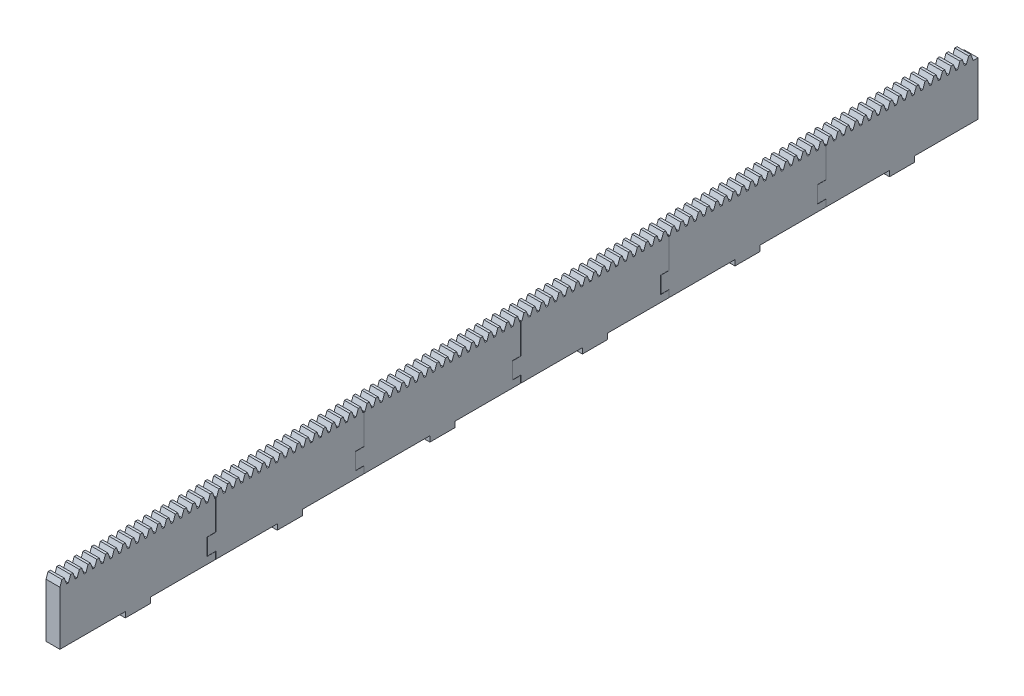
SolidWorks part; units mm, degrees
ref_plane "Спереди" through (0, 0, 0) normal (0, 0, 1) x (1, 0, 0)
ref_plane "Сверху" through (0, 0, 0) normal (0, 1, 0) x (1, 0, 0)
ref_plane "Справа" through (0, 0, 0) normal (1, 0, 0) x (0, 0, -1)
sketch "Эскиз2" plane through (0, 0, 0) normal (1, 0, 0) x (0, 0, -1)
  line L0 (-26.55, -90810.0672) -> (-26.55, -90381.6872) construction
  line L1 (-26.55, -90933.2872) -> (635.45, -90933.2872)
  line L2 (-26.55, -90933.2872) -> (-26.55, -90894.9119)
  line L3 (-26.55, -90894.9119) -> (635.45, -90894.9119)
  line L4 (635.45, -90933.2872) -> (635.45, -90894.9119)
  line L5 (635.45, -90810.0672) -> (635.45, -90381.6872) construction
  line L7 (-26.55, -90933.2872) -> (635.45, -90933.2872) construction
  dimension "D1" = 38.3753
  dimension "База_начала" = 26.55
  dimension "Длина_базы" = 662
  dimension "База_конца" = 635.45
  dimension "База_низа" = 90933.2872
extrude "Бобышка-Вытянуть1" add sketch "Эскиз2" along normal blind 10
sketch "Эскиз3" plane through (10, 0, 0) normal (1, 0, 0) x (0, 0, -1)
  line L0 (-26.55, -90894.9119) -> (-24.9125, -90890.4119)
  line L2 (-24.9125, -90890.4119) -> (-23.2265, -90890.4119)
  line L3 (-23.2265, -90890.4119) -> (-21.589, -90894.9119)
  line L4 (635.45, -90894.9119) -> (-26.55, -90894.9119) construction
  line L5 (-21.589, -90894.9119) -> (-26.55, -90894.9119)
  line L6 (-24.0695, -90890.4119) -> (-24.0695, -90894.9119) construction
  line L7 (-26.55, -90894.9119) -> (-26.55, -90933.2872) construction
  dimension "D1" = 1.686
  dimension "D2" = 4.961
  dimension "D3" = 4.5
extrude "Бобышка-Вытянуть2" add sketch "Эскиз3" against normal blind 10
pattern_linear "Линейный массив1" count 105 spacing 6.2832 along (0, 0, -1) of "Бобышка-Вытянуть2"
sketch "Лапки_рейки_эскиз" plane through (0, 0, 0) normal (1, 0, 0) x (0, 0, -1)
  line L0 (590.5046, -90933.2872) -> (570.5046, -90933.2872)
  line L1 (570.5046, -90933.2872) -> (570.5046, -90925.2872)
  line L2 (570.5046, -90925.2872) -> (590.5046, -90925.2872)
  line L3 (590.5046, -90925.2872) -> (590.5046, -90933.2872)
  line L4 (479.1606, -90933.2872) -> (459.1606, -90933.2872)
  line L5 (459.1606, -90933.2872) -> (459.1606, -90925.2872)
  line L6 (459.1606, -90925.2872) -> (479.1606, -90925.2872)
  line L7 (479.1606, -90925.2872) -> (479.1606, -90933.2872)
  line L8 (369.2048, -90933.2872) -> (349.2048, -90933.2872)
  line L9 (349.2048, -90933.2872) -> (349.2048, -90925.2872)
  line L10 (349.2048, -90925.2872) -> (369.2048, -90925.2872)
  line L11 (369.2048, -90925.2872) -> (369.2048, -90933.2872)
  line L12 (259.2491, -90933.2872) -> (239.2491, -90933.2872)
  line L13 (239.2491, -90933.2872) -> (239.2491, -90925.2872)
  line L14 (239.2491, -90925.2872) -> (259.2491, -90925.2872)
  line L15 (259.2491, -90925.2872) -> (259.2491, -90933.2872)
  line L16 (149.2933, -90933.2872) -> (129.2933, -90933.2872)
  line L17 (129.2933, -90933.2872) -> (129.2933, -90925.2872)
  line L18 (129.2933, -90925.2872) -> (149.2933, -90925.2872)
  line L19 (149.2933, -90925.2872) -> (149.2933, -90933.2872)
  line L20 (39.7431, -90933.2872) -> (19.7431, -90933.2872)
  line L21 (19.7431, -90933.2872) -> (19.7431, -90925.2872)
  line L22 (19.7431, -90925.2872) -> (39.7431, -90925.2872)
  line L23 (39.7431, -90925.2872) -> (39.7431, -90933.2872)
  dimension "X001" = 19.7431
  dimension "X002" = 20
  dimension "X003" = 89.5502
  dimension "X004" = 20
  dimension "X005" = 89.9557
  dimension "X006" = 20
  dimension "X007" = 89.9557
  dimension "X008" = 20
  dimension "X009" = 89.9557
  dimension "X010" = 20
  dimension "X011" = 91.3441
  dimension "X012" = 20
  dimension "Y001" = 90933.2872
  dimension "Y002" = 8
extrude "Лапки_рейки_к_полу" add sketch "Лапки_рейки_эскиз" against normal blind 22
sketch "Шипы_рейки_эскиз" plane through (0, 0, 0) normal (1, 0, 0) x (0, 0, -1)
  line L0 (589.5046, -90937.2872) -> (571.5046, -90937.2872)
  line L1 (571.5046, -90937.2872) -> (571.5046, -90933.2772)
  line L2 (571.5046, -90933.2772) -> (589.5046, -90933.2772)
  line L3 (589.5046, -90933.2772) -> (589.5046, -90937.2872)
  line L4 (478.1606, -90937.2872) -> (460.1606, -90937.2872)
  line L5 (460.1606, -90937.2872) -> (460.1606, -90933.2772)
  line L6 (460.1606, -90933.2772) -> (478.1606, -90933.2772)
  line L7 (478.1606, -90933.2772) -> (478.1606, -90937.2872)
  line L8 (368.2048, -90937.2872) -> (350.2048, -90937.2872)
  line L9 (350.2048, -90937.2872) -> (350.2048, -90933.2772)
  line L10 (350.2048, -90933.2772) -> (368.2048, -90933.2772)
  line L11 (368.2048, -90933.2772) -> (368.2048, -90937.2872)
  line L12 (258.2491, -90937.2872) -> (240.2491, -90937.2872)
  line L13 (240.2491, -90937.2872) -> (240.2491, -90933.2772)
  line L14 (240.2491, -90933.2772) -> (258.2491, -90933.2772)
  line L15 (258.2491, -90933.2772) -> (258.2491, -90937.2872)
  line L16 (148.2933, -90937.2872) -> (130.2933, -90937.2872)
  line L17 (130.2933, -90937.2872) -> (130.2933, -90933.2772)
  line L18 (130.2933, -90933.2772) -> (148.2933, -90933.2772)
  line L19 (148.2933, -90933.2772) -> (148.2933, -90937.2872)
  line L20 (38.7431, -90937.2872) -> (20.7431, -90937.2872)
  line L21 (20.7431, -90937.2872) -> (20.7431, -90933.2772)
  line L22 (20.7431, -90933.2772) -> (38.7431, -90933.2772)
  line L23 (38.7431, -90933.2772) -> (38.7431, -90937.2872)
  dimension "X001" = 20.7431
  dimension "X002" = 18
  dimension "X003" = 91.5502
  dimension "X004" = 18
  dimension "X005" = 91.9557
  dimension "X006" = 18
  dimension "X007" = 91.9557
  dimension "X008" = 18
  dimension "X009" = 91.9557
  dimension "X010" = 18
  dimension "X011" = 93.3441
  dimension "X012" = 18
  dimension "Y001" = 90937.2872
  dimension "Y002" = 4.01
extrude "Шипы_рейки_4мм" add sketch "Шипы_рейки_эскиз" along normal blind 10
sketch "Болты_рейки_эскиз" plane through (0, 0, 0) normal (0, 1, 0) x (1, 0, 0)
  circle A0 centre (-11, 580.5046) radius 2.75
  circle A1 centre (-11, 469.1606) radius 2.75
  circle A2 centre (-11, 359.2048) radius 2.75
  circle A3 centre (-11, 249.2491) radius 2.75
  circle A4 centre (-11, 139.2933) radius 2.75
  circle A5 centre (-11, 29.7431) radius 2.75
  dimension "Диаметр001" = 5.5
  dimension "Диаметр002" = 5.5
  dimension "Диаметр003" = 5.5
  dimension "Диаметр004" = 5.5
  dimension "Диаметр005" = 5.5
  dimension "Диаметр006" = 5.5
  dimension "X001" = 11
  dimension "Y001" = 29.7431
  dimension "Y002" = 109.5502
  dimension "Y003" = 109.9557
  dimension "Y004" = 109.9557
  dimension "Y005" = 109.9557
  dimension "Y006" = 111.3441
extrude "Болты_рейки_М5" cut sketch "Болты_рейки_эскиз" against normal through all and the other way through all
sketch "Гайки_рейки_эскиз" plane through (0, -90925.2872, 0) normal (0, 1, 0) x (1, 0, 0)
  line L0 (-6.208, 580.5046) -> (-8.604, 576.3546)
  line L1 (-8.604, 576.3546) -> (-13.396, 576.3546)
  line L2 (-13.396, 576.3546) -> (-15.792, 580.5046)
  line L3 (-15.792, 580.5046) -> (-13.396, 584.6546)
  line L4 (-13.396, 584.6546) -> (-8.604, 584.6546)
  line L5 (-8.604, 584.6546) -> (-6.208, 580.5046)
  line L6 (-6.208, 469.1606) -> (-8.604, 465.0106)
  line L7 (-8.604, 465.0106) -> (-13.396, 465.0106)
  line L8 (-13.396, 465.0106) -> (-15.792, 469.1606)
  line L9 (-15.792, 469.1606) -> (-13.396, 473.3106)
  line L10 (-13.396, 473.3106) -> (-8.604, 473.3106)
  line L11 (-8.604, 473.3106) -> (-6.208, 469.1606)
  line L12 (-6.208, 359.2048) -> (-8.604, 355.0548)
  line L13 (-8.604, 355.0548) -> (-13.396, 355.0548)
  line L14 (-13.396, 355.0548) -> (-15.792, 359.2048)
  line L15 (-15.792, 359.2048) -> (-13.396, 363.3548)
  line L16 (-13.396, 363.3548) -> (-8.604, 363.3548)
  line L17 (-8.604, 363.3548) -> (-6.208, 359.2048)
  line L18 (-6.208, 249.2491) -> (-8.604, 245.0991)
  line L19 (-8.604, 245.0991) -> (-13.396, 245.0991)
  line L20 (-13.396, 245.0991) -> (-15.792, 249.2491)
  line L21 (-15.792, 249.2491) -> (-13.396, 253.3991)
  line L22 (-13.396, 253.3991) -> (-8.604, 253.3991)
  line L23 (-8.604, 253.3991) -> (-6.208, 249.2491)
  line L24 (-6.208, 139.2933) -> (-8.604, 135.1433)
  line L25 (-8.604, 135.1433) -> (-13.396, 135.1433)
  line L26 (-13.396, 135.1433) -> (-15.792, 139.2933)
  line L27 (-15.792, 139.2933) -> (-13.396, 143.4433)
  line L28 (-13.396, 143.4433) -> (-8.604, 143.4433)
  line L29 (-8.604, 143.4433) -> (-6.208, 139.2933)
  line L30 (-6.208, 29.7431) -> (-8.604, 25.5931)
  line L31 (-8.604, 25.5931) -> (-13.396, 25.5931)
  line L32 (-13.396, 25.5931) -> (-15.792, 29.7431)
  line L33 (-15.792, 29.7431) -> (-13.396, 33.8931)
  line L34 (-13.396, 33.8931) -> (-8.604, 33.8931)
  line L35 (-8.604, 33.8931) -> (-6.208, 29.7431)
  dimension "X001" = 15.792
  dimension "X002" = 2.396
  dimension "X003" = 4.792
  dimension "X004" = 2.396
  dimension "Y001" = 25.5931
  dimension "Y002" = 4.15
  dimension "Y003" = 4.15
  dimension "Y004" = 101.2502
  dimension "Y005" = 4.15
  dimension "Y006" = 4.15
  dimension "Y007" = 101.6557
  dimension "Y008" = 4.15
  dimension "Y009" = 4.15
  dimension "Y010" = 101.6557
  dimension "Y011" = 4.15
  dimension "Y012" = 4.15
  dimension "Y013" = 101.6557
  dimension "Y014" = 4.15
  dimension "Y015" = 4.15
  dimension "Y016" = 103.0441
  dimension "Y017" = 4.15
  dimension "Y018" = 4.15
extrude "Гайки_рейки_М5_4_3мм" cut sketch "Гайки_рейки_эскиз" against normal blind 4.3
sketch "Секции_рейки_эскиз" plane through (0, 0, 0) normal (1, 0, 0) x (0, 0, -1)
  line L0 (525.7842, -90938.2872) -> (525.6342, -90938.2872)
  line L1 (525.6342, -90938.2872) -> (525.6342, -90928.3622)
  line L2 (525.6342, -90928.3622) -> (519.6342, -90928.3622)
  line L3 (519.6342, -90928.3622) -> (519.6342, -90916.2122)
  line L4 (519.6342, -90916.2122) -> (525.6342, -90916.2122)
  line L5 (525.6342, -90916.2122) -> (525.6342, -90888.2872)
  line L6 (525.6342, -90888.2872) -> (525.7842, -90888.2872)
  line L7 (525.7842, -90888.2872) -> (525.7842, -90916.3622)
  line L8 (525.7842, -90916.3622) -> (519.7842, -90916.3622)
  line L9 (519.7842, -90916.3622) -> (519.7842, -90928.2122)
  line L10 (519.7842, -90928.2122) -> (525.7842, -90928.2122)
  line L11 (525.7842, -90928.2122) -> (525.7842, -90938.2872)
  line L12 (412.6869, -90938.2872) -> (412.5369, -90938.2872)
  line L13 (412.5369, -90938.2872) -> (412.5369, -90928.3622)
  line L14 (412.5369, -90928.3622) -> (406.5369, -90928.3622)
  line L15 (406.5369, -90928.3622) -> (406.5369, -90916.2122)
  line L16 (406.5369, -90916.2122) -> (412.5369, -90916.2122)
  line L17 (412.5369, -90916.2122) -> (412.5369, -90888.2872)
  line L18 (412.5369, -90888.2872) -> (412.6869, -90888.2872)
  line L19 (412.6869, -90888.2872) -> (412.6869, -90916.3622)
  line L20 (412.6869, -90916.3622) -> (406.6869, -90916.3622)
  line L21 (406.6869, -90916.3622) -> (406.6869, -90928.2122)
  line L22 (406.6869, -90928.2122) -> (412.6869, -90928.2122)
  line L23 (412.6869, -90928.2122) -> (412.6869, -90938.2872)
  line L24 (305.8727, -90938.2872) -> (305.7227, -90938.2872)
  line L25 (305.7227, -90938.2872) -> (305.7227, -90928.3622)
  line L26 (305.7227, -90928.3622) -> (299.7227, -90928.3622)
  line L27 (299.7227, -90928.3622) -> (299.7227, -90916.2122)
  line L28 (299.7227, -90916.2122) -> (305.7227, -90916.2122)
  line L29 (305.7227, -90916.2122) -> (305.7227, -90888.2872)
  line L30 (305.7227, -90888.2872) -> (305.8727, -90888.2872)
  line L31 (305.8727, -90888.2872) -> (305.8727, -90916.3622)
  line L32 (305.8727, -90916.3622) -> (299.8727, -90916.3622)
  line L33 (299.8727, -90916.3622) -> (299.8727, -90928.2122)
  line L34 (299.8727, -90928.2122) -> (305.8727, -90928.2122)
  line L35 (305.8727, -90928.2122) -> (305.8727, -90938.2872)
  line L36 (192.7754, -90938.2872) -> (192.6254, -90938.2872)
  line L37 (192.6254, -90938.2872) -> (192.6254, -90928.3622)
  line L38 (192.6254, -90928.3622) -> (186.6254, -90928.3622)
  line L39 (186.6254, -90928.3622) -> (186.6254, -90916.2122)
  line L40 (186.6254, -90916.2122) -> (192.6254, -90916.2122)
  line L41 (192.6254, -90916.2122) -> (192.6254, -90888.2872)
  line L42 (192.6254, -90888.2872) -> (192.7754, -90888.2872)
  line L43 (192.7754, -90888.2872) -> (192.7754, -90916.3622)
  line L44 (192.7754, -90916.3622) -> (186.7754, -90916.3622)
  line L45 (186.7754, -90916.3622) -> (186.7754, -90928.2122)
  line L46 (186.7754, -90928.2122) -> (192.7754, -90928.2122)
  line L47 (192.7754, -90928.2122) -> (192.7754, -90938.2872)
  line L48 (85.9612, -90938.2872) -> (85.8112, -90938.2872)
  line L49 (85.8112, -90938.2872) -> (85.8112, -90928.3622)
  line L50 (85.8112, -90928.3622) -> (79.8112, -90928.3622)
  line L51 (79.8112, -90928.3622) -> (79.8112, -90916.2122)
  line L52 (79.8112, -90916.2122) -> (85.8112, -90916.2122)
  line L53 (85.8112, -90916.2122) -> (85.8112, -90888.2872)
  line L54 (85.8112, -90888.2872) -> (85.9612, -90888.2872)
  line L55 (85.9612, -90888.2872) -> (85.9612, -90916.3622)
  line L56 (85.9612, -90916.3622) -> (79.9612, -90916.3622)
  line L57 (79.9612, -90916.3622) -> (79.9612, -90928.2122)
  line L58 (79.9612, -90928.2122) -> (85.9612, -90928.2122)
  line L59 (85.9612, -90928.2122) -> (85.9612, -90938.2872)
  dimension "X001" = 79.8112
  dimension "X002" = 0.15
  dimension "X003" = 5.85
  dimension "X004" = 0.15
  dimension "X005" = 100.6642
  dimension "X006" = 0.15
  dimension "X007" = 5.85
  dimension "X008" = 0.15
  dimension "X009" = 106.9473
  dimension "X010" = 0.15
  dimension "X011" = 5.85
  dimension "X012" = 0.15
  dimension "X013" = 100.6642
  dimension "X014" = 0.15
  dimension "X015" = 5.85
  dimension "X016" = 0.15
  dimension "X017" = 106.9473
  dimension "X018" = 0.15
  dimension "X019" = 5.85
  dimension "X020" = 0.15
  dimension "Y001" = 90938.2872
  dimension "Y002" = 9.925
  dimension "Y003" = 0.15
  dimension "Y004" = 11.85
  dimension "Y005" = 0.15
  dimension "Y006" = 27.925
extrude "Секции_рейки_шип_паз_6шт" cut sketch "Секции_рейки_эскиз" against normal through all and the other way through all
sketch "Торцы_рейки_эскиз" plane through (0, 0, 0) normal (1, 0, 0) x (0, 0, -1)
  line L0 (647.2604, -90939.2872) -> (635.3, -90939.2872)
  line L1 (635.3, -90939.2872) -> (635.3, -90883.2872)
  line L2 (635.3, -90883.2872) -> (647.2604, -90883.2872)
  line L3 (647.2604, -90883.2872) -> (647.2604, -90939.2872)
  line L4 (-26.4, -90939.2872) -> (-36.55, -90939.2872)
  line L5 (-36.55, -90939.2872) -> (-36.55, -90883.2872)
  line L6 (-36.55, -90883.2872) -> (-26.4, -90883.2872)
  line L7 (-26.4, -90883.2872) -> (-26.4, -90939.2872)
  dimension "X001" = 36.55
  dimension "X002" = 10.15
  dimension "X003" = 661.7
  dimension "X004" = 11.9604
  dimension "Y001" = 90939.2872
  dimension "Y002" = 56
extrude "Торцы_рейки_зазор_0_15мм" cut sketch "Торцы_рейки_эскиз" against normal through all and the other way through all
equation "\"Ширина груза\"= 160"
equation "\"Глубина груза\"= 240"
equation "\"Высота груза\"= 160"
equation "\"Ширина ячейки\"= \"Ширина груза\" + 10"
equation "\"Глубина ячейки\"= \"Глубина груза\" + 10"
equation "\"Высота ячейки\"= \"Высота груза\" + 10 + 13"
equation "\"Колво ячеек ширина\"= 2"
equation "\"Колво ячеек высота\"= 2"
equation "\"Толщина стенки\" = \"Толщина тонких панелей\""
equation "\"Крепление дверцы\"= 5 "
equation "\"Ширина рейки\"= \"Толщина шестерни\""
equation "\"Высота рейки\"= 20"
equation "\"Высота пола\" = 2*\"Толщина тонких панелей\""
equation "\"Колво полозьев\"= 5"
equation "\"Отступ рейки\"= 20"
equation "\"Глубина каретки\"= \"Глубина ячейки\" + 30 + \"Мотор Y высота корпуса\" + 20"
equation "\"Длинна рейки\" = (\"Ширина ячейки\"+\"Толщина вертикальных стенок\"+\"Крепление дверцы\")*\"Колво ячеек ширина\"+\"Ширина ячейки выгрузки\"*\"Колво выгрузки\"+\"Толщина вертикальных стенок\"+2*\"Отступ крепления мотора фиксации\"-\"Крепление дверцы\"*\"Колво ячеек ширина\""
equation "\"Отступ шпильки\"= 26"
equation "\"Диаметр шпильки\"= 5"
equation "\"Длинна шпильки\" = (\"Высота ячейки\"+\"Толщина горизонтальных плит\"+\"Высота пола\")*\"Колво ячеек высота\"+2*(\"Толщина горизонтальных плит\"+\"Отступ рейки\")"
equation "\"Ширина пластины\"= 50  "
equation "\"Высота зона выгрузки\"= \"Высота ячейки\" * 2 + \"Толщина стенки\" * 2"
equation "\"Колво выгрузки\"= 1"
equation "\"Ширина ячейки выгрузки\" = \"Ширина ячейки\"+\"Толщина вертикальных стенок\"+2*\"Отступ крепления мотора фиксации\""
equation "\"Отступ крепления мотора фиксации\" = (\"Ширина пластины\"+20-\"Толщина вертикальных стенок\")/2"
equation "\"Мотор X ширина корпуса\"= 42.3"
equation "\"Мотор X высота корпуса\"= 42.3"
equation "\"Мотор X длина корпуса\"= 40"
equation "\"Мотор X вылет вала\"= 19.8"
equation "\"Мотор Y ширина корпуса\"= 42.3"
equation "\"Мотор Y высота корпуса\"= 42.3"
equation "\"Мотор Y длина корпуса\"= 48"
equation "\"Мотор Y вылет вала\"= 30"
equation "\"Мотор Z ширина корпуса\"= 42"
equation "\"Мотор Z высота корпуса\"= 42"
equation "\"Мотор Z длина корпуса\"= 40"
equation "\"Мотор Z вылет вала\"= 23"
equation "\"Мотор диаметр вала ПРЕДВ\"= 5"
equation "\"Мотор шаг крепления ПРЕДВ\"= 31"
equation "\"Мотор диаметр отверстий ПРЕДВ\"= 3"
equation "\"Мотор глубина отверстий ПРЕДВ\"= 4.5"
equation "\"Мотор диаметр буртика ПРЕДВ\"= 22"
equation "\"Мотор высота буртика ПРЕДВ\"= 2"
equation "\"Мотор диаметр шкива ПРЕДВ\"= 16"
equation "\"Мотор длина шкива ПРЕДВ\"= 12"
equation "\"Мотор отступ шкива ПРЕДВ\"= 5"
equation "\"Мотор X шаг градусов\"= 1.8"
equation "\"Мотор Y шаг градусов\"= 1.8"
equation "\"Мотор Z шаг градусов\"= 1.8"
equation "\"Мотор Y диаметр ротора\"= 25.78"
equation "\"Толщина шестерни\"= 10"
equation "\"D1@Эскиз2\" = \"Высота рейки от пола\""
equation "\"D1@Бобышка-Вытянуть1\"=\"Толщина шестерни\""
equation "\"D1@Бобышка-Вытянуть2\"=\"Толщина шестерни\""
equation "\"Высота рейки от пола\"= 38.3752522580543"
equation "\"X001@Лапки_рейки_эскиз\" = \"Привязка_X001_Лапки_рейки_эскиз\""
equation "\"X003@Лапки_рейки_эскиз\" = -1*((\"Крепление рейки 2\"-\"Смещение рейки по Z\"+(10))-(\"Крепление рейки 1\"-\"Смещение рейки по Z\"+(-10)))"
equation "\"X005@Лапки_рейки_эскиз\" = -1*((\"Крепление рейки 3\"-\"Смещение рейки по Z\"+(10))-(\"Крепление рейки 2\"-\"Смещение рейки по Z\"+(-10)))"
equation "\"X007@Лапки_рейки_эскиз\" = -1*((\"Крепление рейки 4\"-\"Смещение рейки по Z\"+(10))-(\"Крепление рейки 3\"-\"Смещение рейки по Z\"+(-10)))"
equation "\"X009@Лапки_рейки_эскиз\" = -1*((\"Крепление рейки 5\"-\"Смещение рейки по Z\"+(10))-(\"Крепление рейки 4\"-\"Смещение рейки по Z\"+(-10)))"
equation "\"X011@Лапки_рейки_эскиз\" = -1*((\"Крепление рейки 6\"-\"Смещение рейки по Z\"+(10))-(\"Крепление рейки 5\"-\"Смещение рейки по Z\"+(-10)))"
equation "\"X001@Шипы_рейки_эскиз\" = \"Привязка_X001_Шипы_рейки_эскиз\""
equation "\"X003@Шипы_рейки_эскиз\" = -1*((\"Крепление рейки 2\"-\"Смещение рейки по Z\"+(9))-(\"Крепление рейки 1\"-\"Смещение рейки по Z\"+(-9)))"
equation "\"X005@Шипы_рейки_эскиз\" = -1*((\"Крепление рейки 3\"-\"Смещение рейки по Z\"+(9))-(\"Крепление рейки 2\"-\"Смещение рейки по Z\"+(-9)))"
equation "\"X007@Шипы_рейки_эскиз\" = -1*((\"Крепление рейки 4\"-\"Смещение рейки по Z\"+(9))-(\"Крепление рейки 3\"-\"Смещение рейки по Z\"+(-9)))"
equation "\"X009@Шипы_рейки_эскиз\" = -1*((\"Крепление рейки 5\"-\"Смещение рейки по Z\"+(9))-(\"Крепление рейки 4\"-\"Смещение рейки по Z\"+(-9)))"
equation "\"X011@Шипы_рейки_эскиз\" = -1*((\"Крепление рейки 6\"-\"Смещение рейки по Z\"+(9))-(\"Крепление рейки 5\"-\"Смещение рейки по Z\"+(-9)))"
equation "\"Y001@Болты_рейки_эскиз\" = \"Привязка_Y001_Болты_рейки_эскиз\""
equation "\"Y002@Болты_рейки_эскиз\" = -1*((\"Крепление рейки 2\"-\"Смещение рейки по Z\"+(0))-(\"Крепление рейки 1\"-\"Смещение рейки по Z\"+(0)))"
equation "\"Y003@Болты_рейки_эскиз\" = -1*((\"Крепление рейки 3\"-\"Смещение рейки по Z\"+(0))-(\"Крепление рейки 2\"-\"Смещение рейки по Z\"+(0)))"
equation "\"Y004@Болты_рейки_эскиз\" = -1*((\"Крепление рейки 4\"-\"Смещение рейки по Z\"+(0))-(\"Крепление рейки 3\"-\"Смещение рейки по Z\"+(0)))"
equation "\"Y005@Болты_рейки_эскиз\" = -1*((\"Крепление рейки 5\"-\"Смещение рейки по Z\"+(0))-(\"Крепление рейки 4\"-\"Смещение рейки по Z\"+(0)))"
equation "\"Y006@Болты_рейки_эскиз\" = -1*((\"Крепление рейки 6\"-\"Смещение рейки по Z\"+(0))-(\"Крепление рейки 5\"-\"Смещение рейки по Z\"+(0)))"
equation "\"Y001@Гайки_рейки_эскиз\" = \"Привязка_Y001_Гайки_рейки_эскиз\""
equation "\"Y004@Гайки_рейки_эскиз\" = -1*((\"Крепление рейки 2\"-\"Смещение рейки по Z\"+(4.15))-(\"Крепление рейки 1\"-\"Смещение рейки по Z\"+(-4.15)))"
equation "\"Y007@Гайки_рейки_эскиз\" = -1*((\"Крепление рейки 3\"-\"Смещение рейки по Z\"+(4.15))-(\"Крепление рейки 2\"-\"Смещение рейки по Z\"+(-4.15)))"
equation "\"Y010@Гайки_рейки_эскиз\" = -1*((\"Крепление рейки 4\"-\"Смещение рейки по Z\"+(4.15))-(\"Крепление рейки 3\"-\"Смещение рейки по Z\"+(-4.15)))"
equation "\"Y013@Гайки_рейки_эскиз\" = -1*((\"Крепление рейки 5\"-\"Смещение рейки по Z\"+(4.15))-(\"Крепление рейки 4\"-\"Смещение рейки по Z\"+(-4.15)))"
equation "\"Y016@Гайки_рейки_эскиз\" = -1*((\"Крепление рейки 6\"-\"Смещение рейки по Z\"+(4.15))-(\"Крепление рейки 5\"-\"Смещение рейки по Z\"+(-4.15)))"
equation "\"X003@Торцы_рейки_эскиз\" = \"Длина рейки для печати\""
equation "\"Толщина тонких панелей\" = 6"
equation "\"Толщина вертикальных стенок\" = 6"
equation "\"Толщина горизонтальных плит\" = 6"
equation "\"Базовая высота корпуса\"= (\"Высота ячейки\"+\"Толщина тонких панелей\"+\"Высота пола\")*\"Колво ячеек высота\"+6*\"Толщина тонких панелей\"+\"Мотор X ширина корпуса\"+\"Мотор Y ширина корпуса\"+75"
equation "\"Высота корпуса\"= (\"Высота ячейки\"+\"Толщина горизонтальных плит\"+\"Высота пола\")*\"Колво ячеек высота\"+2*\"Толщина горизонтальных плит\"+4*\"Толщина тонких панелей\"+\"Мотор X ширина корпуса\"+\"Мотор Y ширина корпуса\"+75"
equation "\"Смещение центра корпуса\"= (\"Высота корпуса\"-\"Базовая высота корпуса\")/2-(\"Толщина горизонтальных плит\"-\"Толщина тонких панелей\")"
equation "\"Отметка пола\"= -\"Базовая высота корпуса\"/2+\"Толщина тонких панелей\""
equation "\"Отметка потолка\"= \"Отметка пола\"+\"Высота корпуса\"-2*\"Толщина горизонтальных плит\""
equation "\"Отметка верхней полки\"= \"Отметка потолка\"-(28+\"Толщина тонких панелей\")-\"Высота ячейки\"-\"Высота пола\""
equation "\"Отметка нижней полки\"= \"Отметка верхней полки\"-\"Высота ячейки\"-\"Высота пола\"-\"Толщина горизонтальных плит\""
equation "\"X001@Торцы_рейки_эскиз\" = \"Длинна рейки\"-\"База_конца@Эскиз2\"+10"
equation "\"dT\"= (\"Толщина вертикальных стенок\"-\"Толщина тонких панелей\")"
equation "\"dW\"= \"Ширина ячейки\"-430+2*\"dT\"/3"
equation "\"Торцевой зазор рейки\"= 0.15"
equation "\"Зазор стыка рейки\"= 0.15"
equation "\"Длина шипа стыка рейки\"= 6"
equation "\"Шаг зубьев рейки\"= 2*pi"
equation "\"Начало рейки для печати\"= \"Длинна рейки\"-\"База_конца@Эскиз2\"-\"Торцевой зазор рейки\""
equation "\"Длина рейки для печати\"= \"Длинна рейки\"-2*\"Торцевой зазор рейки\""
equation "\"Ноль впадин рейки\"= \"Длинна рейки\"-\"База_конца@Эскиз2\"-(\"D2@Эскиз3\"+\"Шаг зубьев рейки\")/2"
equation "\"Стык рейки 1\"= \"Ноль впадин рейки\"-\"Шаг зубьев рейки\"*int((\"Ноль впадин рейки\"-(\"Начало рейки для печати\"-1*\"Длина рейки для печати\"/6))/\"Шаг зубьев рейки\"+0.5)"
equation "\"Стык рейки 2\"= \"Ноль впадин рейки\"-\"Шаг зубьев рейки\"*int((\"Ноль впадин рейки\"-(\"Начало рейки для печати\"-2*\"Длина рейки для печати\"/6))/\"Шаг зубьев рейки\"+0.5)"
equation "\"Стык рейки 3\"= \"Ноль впадин рейки\"-\"Шаг зубьев рейки\"*int((\"Ноль впадин рейки\"-(\"Начало рейки для печати\"-3*\"Длина рейки для печати\"/6))/\"Шаг зубьев рейки\"+0.5)"
equation "\"Стык рейки 4\"= \"Ноль впадин рейки\"-\"Шаг зубьев рейки\"*int((\"Ноль впадин рейки\"-(\"Начало рейки для печати\"-4*\"Длина рейки для печати\"/6))/\"Шаг зубьев рейки\"+0.5)"
equation "\"Стык рейки 5\"= \"Ноль впадин рейки\"-\"Шаг зубьев рейки\"*int((\"Ноль впадин рейки\"-(\"Начало рейки для печати\"-5*\"Длина рейки для печати\"/6))/\"Шаг зубьев рейки\"+0.5)"
equation "\"X001@Секции_рейки_эскиз\" = 1*((\"Стык рейки 1\"+\"Длина шипа стыка рейки\"+\"Зазор стыка рейки\"/2)-0)"
equation "\"X002@Секции_рейки_эскиз\" = -1*((\"Стык рейки 1\"+\"Длина шипа стыка рейки\"-\"Зазор стыка рейки\"/2)-(\"Стык рейки 1\"+\"Длина шипа стыка рейки\"+\"Зазор стыка рейки\"/2))"
equation "\"X003@Секции_рейки_эскиз\" = -1*((\"Стык рейки 1\"+\"Зазор стыка рейки\"/2)-(\"Стык рейки 1\"+\"Длина шипа стыка рейки\"-\"Зазор стыка рейки\"/2))"
equation "\"X004@Секции_рейки_эскиз\" = -1*((\"Стык рейки 1\"-\"Зазор стыка рейки\"/2)-(\"Стык рейки 1\"+\"Зазор стыка рейки\"/2))"
equation "\"X005@Секции_рейки_эскиз\" = -1*((\"Стык рейки 2\"+\"Длина шипа стыка рейки\"+\"Зазор стыка рейки\"/2)-(\"Стык рейки 1\"-\"Зазор стыка рейки\"/2))"
equation "\"X006@Секции_рейки_эскиз\" = -1*((\"Стык рейки 2\"+\"Длина шипа стыка рейки\"-\"Зазор стыка рейки\"/2)-(\"Стык рейки 2\"+\"Длина шипа стыка рейки\"+\"Зазор стыка рейки\"/2))"
equation "\"X007@Секции_рейки_эскиз\" = -1*((\"Стык рейки 2\"+\"Зазор стыка рейки\"/2)-(\"Стык рейки 2\"+\"Длина шипа стыка рейки\"-\"Зазор стыка рейки\"/2))"
equation "\"X008@Секции_рейки_эскиз\" = -1*((\"Стык рейки 2\"-\"Зазор стыка рейки\"/2)-(\"Стык рейки 2\"+\"Зазор стыка рейки\"/2))"
equation "\"X009@Секции_рейки_эскиз\" = -1*((\"Стык рейки 3\"+\"Длина шипа стыка рейки\"+\"Зазор стыка рейки\"/2)-(\"Стык рейки 2\"-\"Зазор стыка рейки\"/2))"
equation "\"X010@Секции_рейки_эскиз\" = -1*((\"Стык рейки 3\"+\"Длина шипа стыка рейки\"-\"Зазор стыка рейки\"/2)-(\"Стык рейки 3\"+\"Длина шипа стыка рейки\"+\"Зазор стыка рейки\"/2))"
equation "\"X011@Секции_рейки_эскиз\" = -1*((\"Стык рейки 3\"+\"Зазор стыка рейки\"/2)-(\"Стык рейки 3\"+\"Длина шипа стыка рейки\"-\"Зазор стыка рейки\"/2))"
equation "\"X012@Секции_рейки_эскиз\" = -1*((\"Стык рейки 3\"-\"Зазор стыка рейки\"/2)-(\"Стык рейки 3\"+\"Зазор стыка рейки\"/2))"
equation "\"X013@Секции_рейки_эскиз\" = -1*((\"Стык рейки 4\"+\"Длина шипа стыка рейки\"+\"Зазор стыка рейки\"/2)-(\"Стык рейки 3\"-\"Зазор стыка рейки\"/2))"
equation "\"X014@Секции_рейки_эскиз\" = -1*((\"Стык рейки 4\"+\"Длина шипа стыка рейки\"-\"Зазор стыка рейки\"/2)-(\"Стык рейки 4\"+\"Длина шипа стыка рейки\"+\"Зазор стыка рейки\"/2))"
equation "\"X015@Секции_рейки_эскиз\" = -1*((\"Стык рейки 4\"+\"Зазор стыка рейки\"/2)-(\"Стык рейки 4\"+\"Длина шипа стыка рейки\"-\"Зазор стыка рейки\"/2))"
equation "\"X016@Секции_рейки_эскиз\" = -1*((\"Стык рейки 4\"-\"Зазор стыка рейки\"/2)-(\"Стык рейки 4\"+\"Зазор стыка рейки\"/2))"
equation "\"X017@Секции_рейки_эскиз\" = -1*((\"Стык рейки 5\"+\"Длина шипа стыка рейки\"+\"Зазор стыка рейки\"/2)-(\"Стык рейки 4\"-\"Зазор стыка рейки\"/2))"
equation "\"X018@Секции_рейки_эскиз\" = -1*((\"Стык рейки 5\"+\"Длина шипа стыка рейки\"-\"Зазор стыка рейки\"/2)-(\"Стык рейки 5\"+\"Длина шипа стыка рейки\"+\"Зазор стыка рейки\"/2))"
equation "\"X019@Секции_рейки_эскиз\" = -1*((\"Стык рейки 5\"+\"Зазор стыка рейки\"/2)-(\"Стык рейки 5\"+\"Длина шипа стыка рейки\"-\"Зазор стыка рейки\"/2))"
equation "\"X020@Секции_рейки_эскиз\" = -1*((\"Стык рейки 5\"-\"Зазор стыка рейки\"/2)-(\"Стык рейки 5\"+\"Зазор стыка рейки\"/2))"
equation "\"Правый конец рейки\"= -\"Ширина ячейки\"-65"
equation "\"Левый конец рейки\"= \"Правый конец рейки\"+\"Длинна рейки\""
equation "\"Впадина рейки в сборке\"= \"Левый конец рейки\"-(\"Шаг зубьев рейки\"+4.961)/2"
equation "\"Стык рейки в сборке 1\"= \"Впадина рейки в сборке\"-\"Шаг зубьев рейки\"*int((\"Впадина рейки в сборке\"-(\"Левый конец рейки\"-0.15-1*(\"Длинна рейки\"-0.3)/6))/\"Шаг зубьев рейки\"+0.5)"
equation "\"Стык рейки в сборке 2\"= \"Впадина рейки в сборке\"-\"Шаг зубьев рейки\"*int((\"Впадина рейки в сборке\"-(\"Левый конец рейки\"-0.15-2*(\"Длинна рейки\"-0.3)/6))/\"Шаг зубьев рейки\"+0.5)"
equation "\"Стык рейки в сборке 3\"= \"Впадина рейки в сборке\"-\"Шаг зубьев рейки\"*int((\"Впадина рейки в сборке\"-(\"Левый конец рейки\"-0.15-3*(\"Длинна рейки\"-0.3)/6))/\"Шаг зубьев рейки\"+0.5)"
equation "\"Стык рейки в сборке 4\"= \"Впадина рейки в сборке\"-\"Шаг зубьев рейки\"*int((\"Впадина рейки в сборке\"-(\"Левый конец рейки\"-0.15-4*(\"Длинна рейки\"-0.3)/6))/\"Шаг зубьев рейки\"+0.5)"
equation "\"Стык рейки в сборке 5\"= \"Впадина рейки в сборке\"-\"Шаг зубьев рейки\"*int((\"Впадина рейки в сборке\"-(\"Левый конец рейки\"-0.15-5*(\"Длинна рейки\"-0.3)/6))/\"Шаг зубьев рейки\"+0.5)"
equation "\"Крепление рейки 1\"= (\"Левый конец рейки\"-0.15+\"Стык рейки в сборке 1\")/2"
equation "\"Крепление рейки 2\"= (\"Стык рейки в сборке 1\"+\"Стык рейки в сборке 2\")/2"
equation "\"Крепление рейки 3\"= (\"Стык рейки в сборке 2\"+\"Стык рейки в сборке 3\")/2"
equation "\"Крепление рейки 4\"= (\"Стык рейки в сборке 3\"+\"Стык рейки в сборке 4\")/2"
equation "\"Крепление рейки 5\"= (\"Стык рейки в сборке 4\"+\"Стык рейки в сборке 5\")/2"
equation "\"Крепление рейки 6\"= (\"Стык рейки в сборке 5\"+\"Правый конец рейки\"+0.15)/2"
equation "\"Смещение рейки по Z\"= \"База_конца@Эскиз2\"+\"Правый конец рейки\""
equation "\"Привязка_X001_Лапки_рейки_эскиз\"= 1*((\"Крепление рейки 1\"-\"Смещение рейки по Z\"+(10))-0)"
equation "\"X002@Лапки_рейки_эскиз\" = -1*((\"Крепление рейки 1\"-\"Смещение рейки по Z\"+(-10))-(\"Крепление рейки 1\"-\"Смещение рейки по Z\"+(10)))"
equation "\"X004@Лапки_рейки_эскиз\" = -1*((\"Крепление рейки 2\"-\"Смещение рейки по Z\"+(-10))-(\"Крепление рейки 2\"-\"Смещение рейки по Z\"+(10)))"
equation "\"X006@Лапки_рейки_эскиз\" = -1*((\"Крепление рейки 3\"-\"Смещение рейки по Z\"+(-10))-(\"Крепление рейки 3\"-\"Смещение рейки по Z\"+(10)))"
equation "\"X008@Лапки_рейки_эскиз\" = -1*((\"Крепление рейки 4\"-\"Смещение рейки по Z\"+(-10))-(\"Крепление рейки 4\"-\"Смещение рейки по Z\"+(10)))"
equation "\"X010@Лапки_рейки_эскиз\" = -1*((\"Крепление рейки 5\"-\"Смещение рейки по Z\"+(-10))-(\"Крепление рейки 5\"-\"Смещение рейки по Z\"+(10)))"
equation "\"X012@Лапки_рейки_эскиз\" = -1*((\"Крепление рейки 6\"-\"Смещение рейки по Z\"+(-10))-(\"Крепление рейки 6\"-\"Смещение рейки по Z\"+(10)))"
equation "\"Привязка_X001_Шипы_рейки_эскиз\"= 1*((\"Крепление рейки 1\"-\"Смещение рейки по Z\"+(9))-0)"
equation "\"X002@Шипы_рейки_эскиз\" = -1*((\"Крепление рейки 1\"-\"Смещение рейки по Z\"+(-9))-(\"Крепление рейки 1\"-\"Смещение рейки по Z\"+(9)))"
equation "\"X004@Шипы_рейки_эскиз\" = -1*((\"Крепление рейки 2\"-\"Смещение рейки по Z\"+(-9))-(\"Крепление рейки 2\"-\"Смещение рейки по Z\"+(9)))"
equation "\"X006@Шипы_рейки_эскиз\" = -1*((\"Крепление рейки 3\"-\"Смещение рейки по Z\"+(-9))-(\"Крепление рейки 3\"-\"Смещение рейки по Z\"+(9)))"
equation "\"X008@Шипы_рейки_эскиз\" = -1*((\"Крепление рейки 4\"-\"Смещение рейки по Z\"+(-9))-(\"Крепление рейки 4\"-\"Смещение рейки по Z\"+(9)))"
equation "\"X010@Шипы_рейки_эскиз\" = -1*((\"Крепление рейки 5\"-\"Смещение рейки по Z\"+(-9))-(\"Крепление рейки 5\"-\"Смещение рейки по Z\"+(9)))"
equation "\"X012@Шипы_рейки_эскиз\" = -1*((\"Крепление рейки 6\"-\"Смещение рейки по Z\"+(-9))-(\"Крепление рейки 6\"-\"Смещение рейки по Z\"+(9)))"
equation "\"Привязка_Y001_Болты_рейки_эскиз\"= 1*((\"Крепление рейки 1\"-\"Смещение рейки по Z\"+(0))-0)"
equation "\"Привязка_Y001_Гайки_рейки_эскиз\"= 1*((\"Крепление рейки 1\"-\"Смещение рейки по Z\"+(4.15))-0)"
equation "\"Y002@Гайки_рейки_эскиз\" = -1*((\"Крепление рейки 1\"-\"Смещение рейки по Z\"+(0))-(\"Крепление рейки 1\"-\"Смещение рейки по Z\"+(4.15)))"
equation "\"Y003@Гайки_рейки_эскиз\" = -1*((\"Крепление рейки 1\"-\"Смещение рейки по Z\"+(-4.15))-(\"Крепление рейки 1\"-\"Смещение рейки по Z\"+(0)))"
equation "\"Y005@Гайки_рейки_эскиз\" = -1*((\"Крепление рейки 2\"-\"Смещение рейки по Z\"+(0))-(\"Крепление рейки 2\"-\"Смещение рейки по Z\"+(4.15)))"
equation "\"Y006@Гайки_рейки_эскиз\" = -1*((\"Крепление рейки 2\"-\"Смещение рейки по Z\"+(-4.15))-(\"Крепление рейки 2\"-\"Смещение рейки по Z\"+(0)))"
equation "\"Y008@Гайки_рейки_эскиз\" = -1*((\"Крепление рейки 3\"-\"Смещение рейки по Z\"+(0))-(\"Крепление рейки 3\"-\"Смещение рейки по Z\"+(4.15)))"
equation "\"Y009@Гайки_рейки_эскиз\" = -1*((\"Крепление рейки 3\"-\"Смещение рейки по Z\"+(-4.15))-(\"Крепление рейки 3\"-\"Смещение рейки по Z\"+(0)))"
equation "\"Y011@Гайки_рейки_эскиз\" = -1*((\"Крепление рейки 4\"-\"Смещение рейки по Z\"+(0))-(\"Крепление рейки 4\"-\"Смещение рейки по Z\"+(4.15)))"
equation "\"Y012@Гайки_рейки_эскиз\" = -1*((\"Крепление рейки 4\"-\"Смещение рейки по Z\"+(-4.15))-(\"Крепление рейки 4\"-\"Смещение рейки по Z\"+(0)))"
equation "\"Y014@Гайки_рейки_эскиз\" = -1*((\"Крепление рейки 5\"-\"Смещение рейки по Z\"+(0))-(\"Крепление рейки 5\"-\"Смещение рейки по Z\"+(4.15)))"
equation "\"Y015@Гайки_рейки_эскиз\" = -1*((\"Крепление рейки 5\"-\"Смещение рейки по Z\"+(-4.15))-(\"Крепление рейки 5\"-\"Смещение рейки по Z\"+(0)))"
equation "\"Y017@Гайки_рейки_эскиз\" = -1*((\"Крепление рейки 6\"-\"Смещение рейки по Z\"+(0))-(\"Крепление рейки 6\"-\"Смещение рейки по Z\"+(4.15)))"
equation "\"Y018@Гайки_рейки_эскиз\" = -1*((\"Крепление рейки 6\"-\"Смещение рейки по Z\"+(-4.15))-(\"Крепление рейки 6\"-\"Смещение рейки по Z\"+(0)))"
equation "\"Y001@Лапки_рейки_эскиз\" = \"База_низа@Эскиз2\"-(0)"
equation "\"Y001@Шипы_рейки_эскиз\" = \"База_низа@Эскиз2\"-(-4)"
equation "\"Y001@Секции_рейки_эскиз\" = \"База_низа@Эскиз2\"-(-5)"
equation "\"Y001@Торцы_рейки_эскиз\" = \"База_низа@Эскиз2\"-(-6)"
